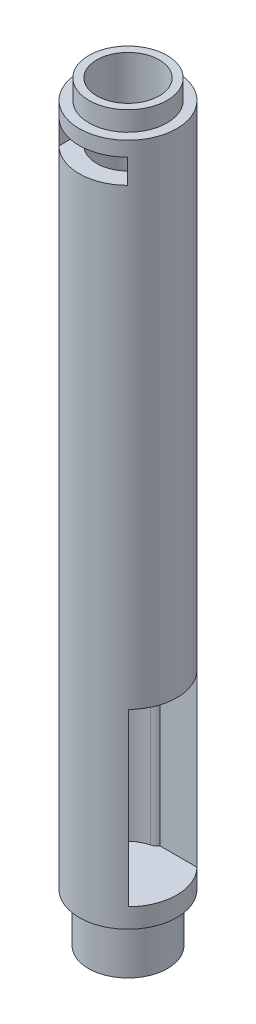
SolidWorks part; units mm, degrees
ref_plane "Front Plane" through (0, 0, 0) normal (0, 0, 1) x (1, 0, 0)
ref_plane "Top Plane" through (0, 0, 0) normal (0, 1, 0) x (1, 0, 0)
ref_plane "Right Plane" through (0, 0, 0) normal (1, 0, 0) x (0, 0, -1)
sketch "Sketch1" plane through (0, 0, 0) normal (0, 1, 0) x (1, 0, 0)
  circle A0 centre (0, 0) radius 12.7
  dimension "D1" = 25.4
extrude "Boss-Extrude1" add sketch "Sketch1" along normal blind 177.8
sketch "Sketch4" plane through (0, 177.8, 0) normal (0, 1, 0) x (1, 0, 0)
  circle A2 centre (0, 0) radius 10.16
  circle A3 centre (0, 0) radius 10.16
  dimension "D1" = 2.54
extrude "Boss-Extrude2" add sketch "Sketch4" along normal blind 5.08
sketch "Sketch5" plane through (0, 182.88, 0) normal (0, 1, 0) x (1, 0, 0)
  circle A0 centre (0, 0) radius 10.16 construction
  circle A1 centre (0, 0) radius 10.16 construction
  circle A2 centre (0, 0) radius 8.128
  dimension "D1" = 2.032
extrude "Cut-Extrude1" cut sketch "Sketch5" against normal through all
sketch "Sketch6" plane through (0, 0, 0) normal (0, -1, 0) x (1, 0, 0)
  circle A0 centre (0, 0) radius 10.287
  circle A1 centre (0, 0) radius 8.128 construction
  circle A2 centre (0, 0) radius 8.128
  dimension "D1" = 20.574
extrude "Boss-Extrude3" add sketch "Sketch6" along normal blind 12.7
sketch "Sketch7" plane through (0, -12.7, 0) normal (0, -1, 0) x (1, 0, 0)
  circle A0 centre (0, 0) radius 12.7 construction
  circle A1 centre (0, 0) radius 12.7
sketch "Sketch8" plane through (0, 182.88, 0) normal (0, 1, 0) x (1, 0, 0)
  circle A0 centre (0, 0) radius 12.7 construction
  circle A1 centre (0, 0) radius 12.7
ref_plane "Plane1" through (0, 2.54, 0) normal (0, -1, 0) x (-1, 0, 0)
split "Split1" trim tools "Plane1" bodies to split 104 resulting bodies 112 113
ref_plane "Plane2" through (13.97, 0, 0) normal (1, 0, 0) x (0, 0, -1)
sketch "Sketch9" plane through (13.97, 0, 0) normal (1, 0, 0) x (0, 0, -1)
  line L0 (-10.287, 0) -> (10.287, 0) construction
  line L1 (-8.89, 5.08) -> (8.89, 5.08)
  line L2 (-8.89, 5.08) -> (-8.89, 49.53)
  line L3 (-8.89, 49.53) -> (8.89, 49.53)
  line L4 (8.89, 5.08) -> (8.89, 49.53)
  line L5 (-8.89, 5.08) -> (8.89, 49.53) construction
  line L6 (-8.89, 49.53) -> (8.89, 5.08) construction
  point P0 (0, 27.305)
  point P5 (0, 0)
  dimension "D1" = 44.45
  dimension "D2" = 17.78
  dimension "D3" = 5.08
extrude "Cut-Extrude2" cut sketch "Sketch9" against normal blind 14.478
fillet "Fillet2" radius 2.54 2 edges at (-0.508, 27.305, -8.1121) (-0.508, 27.305, 8.1121)
sketch "Sketch10" plane through (0, -12.7, 0) normal (0, -1, 0) x (1, 0, 0)
  circle A0 centre (0, 0) radius 8.128 construction
  circle A1 centre (0, 0) radius 8.128
extrude "Boss-Extrude4" add sketch "Sketch10" against normal up to surface (17.78 mm away) up to face at (4.5153, 5.08, 0)
ref_plane "Plane3" through (0, 0, 13.97) normal (0, 0, 1) x (1, 0, 0)
sketch "Sketch11" plane through (0, 0, 13.97) normal (0, 0, 1) x (1, 0, 0)
  line L0 (12.7, 177.8) -> (-12.7, 177.8) construction
  line L1 (-8.89, 167.64) -> (8.89, 167.64)
  line L2 (-8.89, 167.64) -> (-8.89, 173.99)
  line L3 (-8.89, 173.99) -> (8.89, 173.99)
  line L4 (8.89, 167.64) -> (8.89, 173.99)
  line L5 (-8.89, 167.64) -> (8.89, 173.99) construction
  line L6 (-8.89, 173.99) -> (8.89, 167.64) construction
  point P0 (0, 170.815)
  point P5 (0, 0)
  dimension "D1" = 6.35
  dimension "D2" = 17.78
  dimension "D3" = 3.81
extrude "Cut-Extrude3" cut sketch "Sketch11" against normal blind 9.652
fillet "Fillet3" radius 2.54 2 edges at (6.8862, 170.815, 4.318) (-6.8862, 170.815, 4.318)
